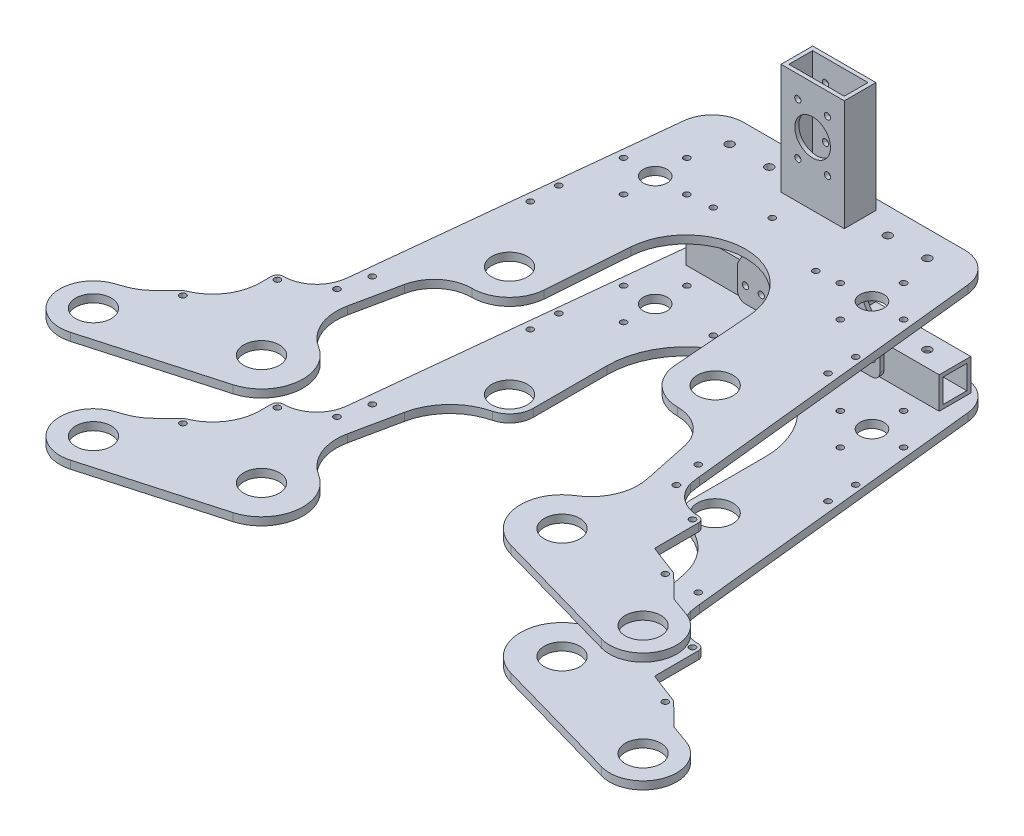
SolidWorks part; units mm, degrees
ref_plane "Alzado" through (0, 0, 0) normal (0, 0, 1) x (1, 0, 0)
ref_plane "Planta" through (0, 0, 0) normal (0, 1, 0) x (1, 0, 0)
ref_plane "Vista lateral" through (0, 0, 0) normal (1, 0, 0) x (0, 0, -1)
sketch "llantas" plane through (0, 0, 0) normal (0, 1, 0) x (1, 0, 0)
  line L0 (0, 221.5734) -> (0, 0) construction
  line L1 (-215.9, 0) -> (0, 0) construction
  circle A0 centre (-93.6625, 101.6) radius 50.8
  circle A1 centre (-215.9, 0) radius 38.1
  circle A2 centre (215.9, 0) radius 38.1
  circle A3 centre (93.6625, 101.6) radius 50.8
  dimension "D1" = 101.6
  dimension "D2" = 42.8625
  dimension "D3" = 177.8
  dimension "D4" = 76.2
  dimension "D5" = 101.6
sketch "cono" plane through (0, 0, 0) normal (1, 0, 0) x (0, 0, -1)
  line L0 (-76.2, 23.114) -> (-22.987, 324.358)
  line L1 (-22.987, 324.358) -> (22.987, 324.358)
  line L2 (0, 324.358) -> (0, 23.114) construction
  line L3 (76.2, 23.114) -> (-76.2, 23.114) construction
  line L4 (-76.2, 23.114) -> (-106.426, 23.114)
  line L5 (-106.426, 23.114) -> (-106.426, 0)
  line L6 (-106.426, 0) -> (106.426, 0)
  line L7 (0, 0) -> (0, 23.114)
  line L8 (-76.2, 23.114) -> (76.2, 23.114)
  line L9 (-80.283, 0) -> (80.283, 0)
  line L10 (221.5734, 0) -> (0, 0) construction
  line L11 (106.426, 23.114) -> (106.426, 0)
  line L12 (76.2, 23.114) -> (106.426, 23.114)
  line L13 (76.2, 23.114) -> (22.987, 324.358)
  line L14 (0, 220.8278) -> (41.275, 220.8278) construction
  dimension "D1" = 324.358
  dimension "D2" = 23.114
  dimension "D3" = 22.987
  dimension "D4" = 152.4
  dimension "D5" = 212.852
  dimension "D6" = 41.275
  dimension "D7" = 220.8278
sketch "Croquis4" plane through (0, 0, 0) normal (0, 1, 0) x (1, 0, 0)
  line L11 (0, 293.4478) -> (0, -300.8756) construction
  circle A36 centre (0, 179.087) radius 32.258
  dimension "D4" = 64.516
ref_plane "Plano1" through (0, 184.15, 0) normal (0, 1, 0) x (1, 0, 0)
sketch "Croquis11" plane through (0, 184.15, 0) normal (0, 1, 0) x (1, 0, 0)
  line L0 (0, -106.426) -> (0, 106.426) construction
  line L1 (-96.4967, 55.808) -> (-110.9593, -55.5389) construction
  line L2 (0, 0) -> (0, -47.7539) construction
  line L3 (-77.6831, 56.5481) -> (-54.5184, -53.3186) construction
  line L4 (-102.0644, -224.6803) -> (-63.9644, -63.6256) construction
  line L5 (-139.2356, -215.8869) -> (-101.1356, -54.8321) construction
  line L6 (0, 0) -> (-82.55, -59.2289) construction
  line L7 (0, 0) -> (0, -106.426) construction
  line L14 (-126.947, -202.253) -> (-226.9506, -237.178) construction
  line L15 (-114.353, -238.3143) -> (-214.3566, -273.2393) construction
  line L16 (0, 293.4478) -> (0, -300.8756) construction
  line L17 (-220.6536, -283.7836) -> (-120.65, -283.7836) construction
  circle A0 centre (0, 0) radius 47.7539 construction
  circle A1 centre (-82.55, -59.2289) radius 50.8
  circle A2 centre (-87.027, 54.578) radius 30
  arc A3 (-77.6831, 56.5481) -> (-96.4967, 55.808) centre (-87.027, 54.578) ccw construction
  arc A4 (-110.9593, -55.5389) -> (-54.5184, -53.3186) centre (-82.55, -59.2289) ccw construction
  arc A6 (-139.2356, -215.8869) -> (-102.0644, -224.6803) centre (-120.65, -220.2836) ccw construction
  arc A7 (-63.9644, -63.6256) -> (-101.1356, -54.8321) centre (-82.55, -59.2289) ccw construction
  circle A12 centre (-120.65, -220.2836) radius 50.8
  circle A13 centre (-220.6536, -255.2086) radius 28.575
  arc A14 (-226.9506, -237.178) -> (-214.3566, -273.2393) centre (-220.6536, -255.2086) ccw construction
  arc A15 (-114.353, -238.3143) -> (-139.2356, -215.8869) centre (-120.65, -220.2836) ccw construction
  dimension "D1" = 101.6
  dimension "D4" = 60
  dimension "D5" = 19.0986
  dimension "D6" = 57.2958
  dimension "D10" = 38.1972
  dimension "D17" = 101.6
  dimension "D13" = 57.15
  dimension "D14" = 38.1972
  dimension "D2" = 101.6
  dimension "D3" = 165.1
  dimension "D8" = 69.85
  dimension "D9" = 12.7
sketch "Croquis40" plane through (0, 184.15, 0) normal (0, 1, 0) x (1, 0, 0)
  line L0 (-117.475, -110.0289) -> (117.475, -110.0289) construction
  line L1 (-117.475, -110.0289) -> (-117.475, -344.9789) construction
  line L2 (117.475, -110.0289) -> (117.475, -344.9789) construction
  line L3 (-117.475, -344.9789) -> (117.475, -344.9789) construction
  line L4 (0, 0) -> (0, -110.0289)
  circle A1 centre (-82.55, -59.2289) radius 50.8 construction
  dimension "D1" = 234.95
ref_plane "Plano2" through (0, 95.25, 0) normal (0, 1, 0) x (1, 0, 0)
sketch "Croquis12" plane through (0, 95.25, 0) normal (0, 1, 0) x (1, 0, 0)
  line L0 (0, 0) -> (0, -63.4576) construction
  circle A0 centre (0, 0) radius 63.4576 construction
  circle A1 centre (-82.55, -59.2289) radius 50.8
  circle A2 centre (-82.55, -59.2289) radius 50.8 construction
sketch "Croquis42" plane through (0, 184.15, 0) normal (0, 1, 0) x (1, 0, 0)
  line L9 (-88.7823, 135.1003) -> (88.7949, 135.1003)
  line L10 (139.6816, -128.9028) -> (114.0528, 112.3831)
  line L11 (-47.6217, 3.5515) -> (-52.471, -61.4721)
  line L12 (-112.3836, -113.6275) -> (-120.3575, -151.7275)
  line L13 (-120.65, -220.2836) -> (-220.6536, -255.2086) construction
  line L14 (-111.5648, -252.3593) -> (-213.299, -281.1746)
  line L15 (0, 226.6032) -> (0, -226.6032) construction
  line L17 (229.5516, -229.7302) -> (214.7311, -224.4111)
  line L18 (-229.5516, -229.7302) -> (-215.5189, -224.8294)
  line L19 (-139.5373, -128.9308) -> (-114.0416, 112.3692)
  line L20 (-126.947, -202.253) -> (-226.9506, -237.178) construction
  line L22 (111.5648, -252.3593) -> (213.299, -281.1746)
  line L23 (112.3836, -113.6275) -> (120.3575, -151.7275)
  line L24 (47.6217, 3.5515) -> (52.471, -61.4721)
  circle A11 centre (-220.6536, -255.2086) radius 14.2875
  circle A17 centre (-120.65, -220.2836) radius 14.2875
  circle A18 centre (-82.55, -59.2289) radius 14.2875
  arc A20 (47.6217, 3.5515) -> (-47.6217, 3.5515) centre (0, 0) ccw
  circle A21 centre (87.027, 62.198) radius 25.4 construction
  circle A22 centre (0, 0) radius 47.7539 construction
  arc A23 (-82.55, -89.3914) -> (-52.471, -61.4721) centre (-82.55, -59.2289) ccw
  arc A24 (-82.55, -89.3914) -> (-112.3836, -113.6275) centre (-82.55, -119.8714) ccw
  arc A25 (-111.5648, -252.3593) -> (-103.1106, -191.933) centre (-120.65, -220.2836) ccw
  arc A26 (-120.3575, -151.7275) -> (-103.1106, -191.933) centre (-83.0655, -159.5323) ccw
  arc A28 (-229.5516, -229.7302) -> (-213.299, -281.1746) centre (-220.6536, -255.2086) ccw
  circle A29 centre (120.65, -220.2836) radius 33.3375 construction
  circle A30 centre (112.427, 62.198) radius 2.4892
  circle A33 centre (-120.65, -220.2836) radius 33.3375 construction
  circle A34 centre (-87.027, 62.198) radius 25.4 construction
  circle A35 centre (-87.027, 87.598) radius 2.4892
  circle A36 centre (-61.627, 62.198) radius 2.4892
  circle A37 centre (-87.027, 36.798) radius 2.4892
  circle A38 centre (-112.427, 62.198) radius 2.4892
  circle A39 centre (87.027, 36.798) radius 2.4892
  circle A40 centre (61.627, 62.198) radius 2.4892
  circle A41 centre (87.027, 87.598) radius 2.4892
  arc A43 (229.5516, -229.7302) -> (213.299, -281.1746) centre (220.6536, -255.2086) cw
  arc A44 (120.3575, -151.7275) -> (103.1106, -191.933) centre (83.0655, -159.5323) cw
  arc A45 (111.5648, -252.3593) -> (103.1106, -191.933) centre (120.65, -220.2836) cw
  arc A46 (82.55, -89.3914) -> (112.3836, -113.6275) centre (82.55, -119.8714) cw
  arc A47 (82.55, -89.3914) -> (52.471, -61.4721) centre (82.55, -59.2289) cw
  circle A48 centre (82.55, -59.2289) radius 14.2875
  circle A49 centre (120.65, -220.2836) radius 14.2875
  circle A50 centre (220.6536, -255.2086) radius 14.2875
  arc A52 (139.6816, -128.9028) -> (214.7311, -224.4111) centre (253.3422, -116.8301) ccw
  arc A53 (-215.5189, -224.8294) -> (-139.5373, -128.9308) centre (-253.2046, -116.9208) ccw
  circle A54 centre (-87.027, 62.198) radius 9.5631
  circle A55 centre (87.027, 62.198) radius 9.5631
  arc A56 (114.0528, 112.3831) -> (88.7949, 135.1003) centre (88.7949, 109.7003) ccw
  arc A57 (-114.0416, 112.3692) -> (-88.7823, 135.1003) centre (-88.7823, 109.7003) cw
  point P18 (0, 0)
  point P40 (111.6399, 135.1003)
  point P52 (-87.027, 62.198)
  point P66 (147.2539, -200.1933)
  point P82 (-111.6399, 135.1003)
  point P83 (0, 0)
  point P84 (0, 0)
  point P85 (87.027, 62.198)
  point P86 (0, 0)
  point P87 (0, 0)
  point P90 (-147.2539, -200.1933)
  point P92 (0, 0)
  dimension "D1" = 28.575
  dimension "D2" = 19.05
  dimension "D3" = 12.7
  dimension "D4" = 15.875
  dimension "D5" = 38.1
  dimension "D7" = 30.48
  dimension "D8" = 50.8
  dimension "D9" = 4.9784
  dimension "D11" = 114.3
  dimension "D12" = 19.1262
  dimension "D13" = 25.4
  dimension "D14" = 241.3
  dimension "D16" = 137.16
  dimension "D18" = 72.9022
  dimension "D19" = 87.027
  dimension "D6" = 38.1
  dimension "D17" = 1.766
  dimension "D10" = 4
extrude "4400-23-P-0501" add sketch "Croquis42" along normal blind 6.35
sketch "Croquis44" plane through (0, 95.25, 0) normal (0, 1, 0) x (1, 0, 0)
  line L1 (-114.0416, 112.3692) -> (-139.5373, -128.9308) construction
  line L3 (-114.0416, 112.3692) -> (-139.5373, -128.9308)
  line L4 (139.6816, -128.9028) -> (114.0528, 112.3831) construction
  line L5 (229.5516, -229.7302) -> (214.7311, -224.4111) construction
  line L6 (111.5648, -252.3593) -> (213.299, -281.1746) construction
  line L7 (112.3836, -113.6275) -> (120.3575, -151.7275) construction
  line L9 (88.7949, 135.1003) -> (-88.7823, 135.1003) construction
  line L10 (-120.3575, -151.7275) -> (-112.3836, -113.6275) construction
  line L11 (-213.299, -281.1746) -> (-111.5648, -252.3593) construction
  line L12 (-215.5189, -224.8294) -> (-229.5516, -229.7302) construction
  line L13 (139.6816, -128.9028) -> (114.0528, 112.3831)
  line L14 (229.5516, -229.7302) -> (214.7311, -224.4111)
  line L15 (111.5648, -252.3593) -> (213.299, -281.1746)
  line L16 (112.3836, -113.6275) -> (120.3575, -151.7275)
  line L19 (-120.3575, -151.7275) -> (-112.3836, -113.6275)
  line L20 (-213.299, -281.1746) -> (-111.5648, -252.3593)
  line L21 (-215.5189, -224.8294) -> (-229.5516, -229.7302)
  line L22 (-63.4576, -59.2289) -> (-63.4576, 0)
  line L23 (63.4576, -59.2289) -> (63.4576, 0)
  line L24 (0, 0) -> (0, -147.841) construction
  line L25 (88.7949, 135.1003) -> (-88.7823, 135.1003)
  arc A0 (-215.5189, -224.8294) -> (-139.5373, -128.9308) centre (-253.2046, -116.9208) ccw construction
  arc A2 (-215.5189, -224.8294) -> (-139.5373, -128.9308) centre (-253.2046, -116.9208) ccw
  arc A5 (139.6816, -128.9028) -> (214.7311, -224.4111) centre (253.3422, -116.8301) ccw construction
  arc A6 (213.299, -281.1746) -> (229.5516, -229.7302) centre (220.6536, -255.2086) ccw construction
  arc A7 (103.1106, -191.933) -> (111.5648, -252.3593) centre (120.65, -220.2836) ccw construction
  arc A8 (103.1106, -191.933) -> (120.3575, -151.7275) centre (83.0655, -159.5323) ccw construction
  arc A11 (114.0528, 112.3831) -> (88.7949, 135.1003) centre (88.7949, 109.7003) ccw construction
  arc A14 (-120.3575, -151.7275) -> (-103.1106, -191.933) centre (-83.0655, -159.5323) ccw construction
  arc A15 (-111.5648, -252.3593) -> (-103.1106, -191.933) centre (-120.65, -220.2836) ccw construction
  arc A16 (-229.5516, -229.7302) -> (-213.299, -281.1746) centre (-220.6536, -255.2086) ccw construction
  arc A18 (139.6816, -128.9028) -> (214.7311, -224.4111) centre (253.3422, -116.8301) ccw
  arc A19 (213.299, -281.1746) -> (229.5516, -229.7302) centre (220.6536, -255.2086) ccw
  arc A20 (103.1106, -191.933) -> (111.5648, -252.3593) centre (120.65, -220.2836) ccw
  arc A21 (103.1106, -191.933) -> (120.3575, -151.7275) centre (83.0655, -159.5323) ccw
  arc A27 (-120.3575, -151.7275) -> (-103.1106, -191.933) centre (-83.0655, -159.5323) ccw
  arc A28 (-111.5648, -252.3593) -> (-103.1106, -191.933) centre (-120.65, -220.2836) ccw
  arc A29 (-229.5516, -229.7302) -> (-213.299, -281.1746) centre (-220.6536, -255.2086) ccw
  circle A30 centre (87.027, 62.198) radius 9.5631 construction
  circle A31 centre (87.027, 36.798) radius 2.4892 construction
  circle A32 centre (112.427, 62.198) radius 2.4892 construction
  circle A33 centre (87.027, 87.598) radius 2.4892 construction
  circle A34 centre (61.627, 62.198) radius 2.4892 construction
  circle A35 centre (-87.027, 62.198) radius 9.5631 construction
  circle A37 centre (-87.027, 87.598) radius 2.4892 construction
  circle A38 centre (-112.427, 62.198) radius 2.4892 construction
  circle A39 centre (-87.027, 36.798) radius 2.4892 construction
  circle A40 centre (220.6536, -255.2086) radius 14.2875 construction
  circle A41 centre (120.65, -220.2836) radius 14.2875 construction
  circle A42 centre (82.55, -59.2289) radius 14.2875 construction
  circle A43 centre (-82.55, -59.2289) radius 14.2875 construction
  circle A44 centre (-120.65, -220.2836) radius 14.2875 construction
  circle A45 centre (-220.6536, -255.2086) radius 14.2875 construction
  circle A46 centre (87.027, 62.198) radius 9.5631
  circle A47 centre (87.027, 36.798) radius 2.4892
  circle A48 centre (112.427, 62.198) radius 2.4892
  circle A49 centre (87.027, 87.598) radius 2.4892
  circle A50 centre (61.627, 62.198) radius 2.4892
  circle A51 centre (-87.027, 62.198) radius 9.5631
  circle A53 centre (-87.027, 87.598) radius 2.4892
  circle A54 centre (-112.427, 62.198) radius 2.4892
  circle A55 centre (-87.027, 36.798) radius 2.4892
  circle A56 centre (220.6536, -255.2086) radius 14.2875
  circle A57 centre (120.65, -220.2836) radius 14.2875
  circle A58 centre (82.55, -59.2289) radius 14.2875
  circle A59 centre (-82.55, -59.2289) radius 14.2875
  circle A60 centre (-120.65, -220.2836) radius 14.2875
  circle A61 centre (-220.6536, -255.2086) radius 14.2875
  arc A62 (63.4576, 0) -> (-63.4576, 0) centre (0, 0) ccw
  arc A63 (-88.7823, 135.1003) -> (-114.0416, 112.3692) centre (-88.7823, 109.7003) ccw construction
  arc A64 (-63.4576, -59.2289) -> (-77.9, -77.7463) centre (-82.55, -59.2289) cw
  arc A65 (-112.3836, -113.6275) -> (-77.9, -77.7463) centre (-66.477, -123.2353) cw
  circle A66 centre (0, 0) radius 63.4576 construction
  arc A67 (112.3836, -113.6275) -> (77.9, -77.7463) centre (66.477, -123.2353) ccw
  arc A68 (63.4576, -59.2289) -> (77.9, -77.7463) centre (82.55, -59.2289) ccw
  arc A69 (114.0528, 112.3831) -> (88.7949, 135.1003) centre (88.7949, 109.7003) ccw
  arc A70 (-88.7823, 135.1003) -> (-114.0416, 112.3692) centre (-88.7823, 109.7003) ccw
extrude "4400-23-P-0502" add sketch "Croquis44" along normal blind 6.35
sketch "Croquis45" plane through (0, 95.25, 0) normal (0, -1, 0) x (1, 0, 0)
  line L7 (-126.947, 202.253) -> (-226.9506, 237.178) construction
  circle A0 centre (-189.6273, 213.7178) radius 4.7625 construction
  circle A1 centre (-189.6273, 213.7178) radius 2.4892
  circle A6 centre (-220.6536, 255.2086) radius 38.1
  circle A7 centre (-220.6536, 255.2086) radius 38.1 construction
  circle A9 centre (-120.65, 220.2836) radius 63.5
  circle A10 centre (-120.65, 220.2836) radius 63.5 construction
  dimension "D1" = 9.525
  dimension "D2" = 4.9784
  dimension "D5" = 5.08
  dimension "D3" = 9.525
  dimension "D4" = 12.7
sketch "Croquis46" plane through (0, 190.5, 0) normal (0, 1, 0) x (1, 0, 0)
  line L0 (-184.6841, -242.6467) -> (-180.5992, -241.2201) construction
  line L1 (-126.947, -202.253) -> (-226.9506, -237.178) construction
  line L2 (-220.6536, -255.2086) -> (-120.65, -220.2836) construction
  line L3 (-182.6417, -241.9334) -> (-193.6494, -210.4142) construction
  line L4 (-166.6601, -156.7836) -> (-120.65, -156.7836) construction
  line L5 (-215.1779, -224.7097) -> (-196.9699, -207.0002)
  line L6 (-171.5935, -196.9465) -> (-195.3397, -205.9618)
  line L7 (-171.5935, -196.9465) -> (-171.4226, -161.5232)
  line L8 (0, 0) -> (0, -195.4432) construction
  line L9 (166.6601, -156.7836) -> (120.65, -156.7836) construction
  line L10 (182.6417, -241.9334) -> (193.6494, -210.4142) construction
  line L11 (220.6536, -255.2086) -> (120.65, -220.2836) construction
  line L12 (184.6841, -242.6467) -> (180.5992, -241.2201) construction
  line L13 (171.524, -196.8756) -> (171.4226, -161.5232)
  line L14 (171.524, -196.8756) -> (195.3397, -205.9618)
  line L15 (215.1779, -224.7097) -> (196.9699, -207.0002)
  circle A0 centre (-220.6536, -255.2086) radius 38.1 construction
  circle A1 centre (-193.6494, -210.4142) radius 4.7625 construction
  circle A2 centre (-193.6494, -210.4142) radius 2.4892
  circle A3 centre (-166.6601, -161.5461) radius 4.7625 construction
  circle A4 centre (-166.6601, -161.5461) radius 2.4892
  arc A5 (-215.5189, -224.8294) -> (-139.5373, -128.9308) centre (-253.2046, -116.9208) ccw construction
  circle A6 centre (-120.65, -220.2836) radius 63.5 construction
  arc A7 (-196.9699, -207.0002) -> (-195.3397, -205.9618) centre (-193.6494, -210.4142) cw
  arc A8 (-171.4226, -161.5232) -> (-166.6601, -156.7836) centre (-166.6601, -161.5461) cw
  arc A9 (-166.6601, -156.7836) -> (-140.1904, -134.0169) centre (-166.6601, -130.0127) ccw
  arc A10 (-215.1779, -224.7097) -> (-140.1904, -134.0169) centre (-253.2046, -116.9208) ccw
  circle A11 centre (166.6601, -161.5461) radius 4.7625 construction
  circle A12 centre (193.6494, -210.4142) radius 4.7625 construction
  arc A13 (215.1779, -224.7097) -> (140.1904, -134.0169) centre (253.2046, -116.9208) cw
  arc A14 (166.6601, -156.7836) -> (140.1904, -134.0169) centre (166.6601, -130.0127) cw
  arc A15 (171.4226, -161.5232) -> (166.6601, -156.7836) centre (166.6601, -161.5461) ccw
  arc A16 (196.9699, -207.0002) -> (195.3397, -205.9618) centre (193.6494, -210.4142) ccw
  circle A17 centre (166.6601, -161.5461) radius 2.4892
  circle A18 centre (193.6494, -210.4142) radius 2.4892
  point P20 (-182.6417, -241.9334)
  point P59 (171.7892, -196.616)
  point P60 (0, 0)
  arc M29 (214.7311, -224.4111) -> (139.6816, -128.9028) centre (253.3422, -116.8301) cw
  arc M35 (-139.5373, -128.9308) -> (-215.5189, -224.8294) centre (-253.2046, -116.9208) cw
  dimension "D1" = 4.9784
  dimension "D2" = 9.525
  dimension "D4" = 6.35
  dimension "D3" = 9.525
  dimension "D5" = 25.4
extrude "Saliente-Extruir2" add sketch "Croquis46" against normal up to surface (6.35 mm away) contours A9 A8 L7 A4 M35 | A7 L5 A2 L6 M35 | L13 A15 A14 A17 M29 | A18 L15 A16 L14 M29 region at (-160.3128, 190.5, 168.9154) region at (-205.7136, 190.5, 216.2254) region at (171.6867, 190.5, 196.9931) region at (160.416, 190.5, 168.894) up to face at (-0.0173, 184.15, 113.2201)
fillet "Redondeo1" radius 38.1 2 edges at (-215.1779, 187.325, 224.7097) (-171.5935, 187.325, 196.9465)
extrude "Saliente-Extruir3" add sketch "Croquis46<3>" against normal up to surface (95.25 mm away) from surface contours A9 A8 L7 A4 M35 | A7 L5 A2 L6 M35 | L13 A15 A14 A17 M29 | A18 L15 A16 L14 M29 region at (-160.3128, 190.5, 168.9154) region at (-205.7136, 190.5, 216.2254) region at (171.6867, 190.5, 196.9931) region at (160.416, 190.5, 168.894) up to face at (-0.0173, 95.25, 111.4477) starting at face at (-120.65, 101.6, 234.5711)
sketch "Croquis46<3>" plane through (0, 190.5, 0) normal (0, 1, 0) x (1, 0, 0) same geometry as "Croquis46"
fillet "Redondeo2" radius 38.1 2 edges at (-215.1779, 98.425, 224.7097) (-171.5935, 98.425, 196.9465)
sketch "Croquis47" plane through (0, 190.5, 0) normal (0, 1, 0) x (1, 0, 0)
  line L0 (-139.2356, -215.8869) -> (-101.1356, -54.8321) construction
  line L1 (88.7949, 135.1003) -> (-88.7823, 135.1003) construction
  line L4 (0, 0) -> (0, -211.1114) construction
  line L9 (-96.4967, 55.808) -> (-110.9593, -55.5389) construction
  line L14 (-77.6831, 56.5481) -> (-54.5184, -53.3186) construction
  circle A0 centre (-136.2788, -144.0836) radius 4.7625 construction
  circle A1 centre (-136.2788, -144.0836) radius 2.4892
  circle A2 centre (-130.8514, -121.1414) radius 4.7625 construction
  circle A3 centre (-130.8514, -121.1414) radius 2.4892
  circle A5 centre (-120.65, -220.2836) radius 63.5 construction
  circle A7 centre (-82.55, -59.2289) radius 50.8 construction
  circle A8 centre (130.8514, -121.1414) radius 2.4892
  circle A9 centre (130.8514, -121.1414) radius 4.7625 construction
  circle A10 centre (136.2788, -144.0836) radius 2.4892
  circle A11 centre (136.2788, -144.0836) radius 4.7625 construction
  circle A12 centre (-119.5187, -5.5845) radius 2.4892
  circle A13 centre (-119.5187, -5.5845) radius 4.7625 construction
  circle A14 centre (-119.1503, 16.9711) radius 2.4892
  circle A15 centre (-119.1503, 16.9711) radius 4.7625 construction
  circle A17 centre (-87.027, 54.578) radius 30 construction
  circle A18 centre (119.1503, 16.9711) radius 4.7625 construction
  circle A19 centre (119.1503, 16.9711) radius 2.4892
  circle A20 centre (119.5187, -5.5845) radius 4.7625 construction
  circle A21 centre (119.5187, -5.5845) radius 2.4892
  circle A22 centre (-43.3745, 60.7655) radius 4.7625 construction
  circle A23 centre (-43.3745, 60.7655) radius 2.4892
  circle A24 centre (43.3745, 60.7655) radius 2.4892
  circle A25 centre (43.3745, 60.7655) radius 4.7625 construction
  circle A26 centre (-11.0144, 80.167) radius 4.7625 construction
  circle A27 centre (-11.0144, 80.167) radius 2.4892
  circle A28 centre (-41.8594, 63.6221) radius 2.4892
  circle A29 centre (-41.8594, 63.6221) radius 4.7625 construction
  circle A31 centre (0, 0) radius 63.4576 construction
  circle A32 centre (41.8594, 63.6221) radius 2.4892
  circle A33 centre (41.8594, 63.6221) radius 4.7625 construction
  dimension "D1" = 4.9784
  dimension "D2" = 9.525
  dimension "D3" = 8.89
  dimension "D4" = 8.89
  dimension "D5" = 12.7
  dimension "D6" = 6.35
  dimension "D7" = 9.525
  dimension "D8" = 4.9784
  dimension "D9" = 12.7
  dimension "D10" = 10.16
  dimension "D11" = 25.4
  dimension "D12" = 25.4
  dimension "D13" = 4.9784
  dimension "D14" = 9.525
  dimension "D15" = 8.89
  dimension "D16" = 74.3347
  dimension "D17" = 9.525
  dimension "D18" = 4.9784
  dimension "D19" = 12.7
  dimension "D20" = 65.3447
  dimension "D21" = 12.7
  dimension "D22" = 31.75
extrude "Cortar-Extruir1" cut sketch "Croquis47" against normal through all contours A27 | A19 | A21 | A8 | A10 | A1 | A14 | A12 | A23 A28 | A23 A28 | A3 | A24 region at (-136.2788, 190.5, 144.0836) region at (130.8514, 190.5, 121.1414) region at (136.2788, 190.5, 144.0836) region at (-119.5187, 190.5, 5.5845) region at (-119.1503, 190.5, -16.9711) region at (119.1503, 190.5, -16.9711) region at (119.5187, 190.5, 5.5845) region at (-42.6169, 190.5, -62.1938) region at (-41.6259, 190.5, -64.0622) region at (-11.0144, 190.5, -80.167)
sketch "Croquis48" plane through (0, 101.6, 0) normal (0, 1, 0) x (1, 0, 0)
  line L1 (-101.6, 127) -> (101.6, 127)
  line L2 (-101.6, 127) -> (-101.6, 101.6)
  line L3 (-101.6, 101.6) -> (101.6, 101.6)
  line L4 (101.6, 127) -> (101.6, 101.6)
  line L5 (-101.6, 127) -> (101.6, 101.6) construction
  line L6 (-101.6, 101.6) -> (101.6, 127) construction
  point P0 (0, 114.3)
  dimension "D1" = 25.4
  dimension "D2" = 203.2
  dimension "D3" = 114.3
extrude "Saliente-Extruir4" add sketch "Croquis48" along normal blind 25.4 from surface separate body starting at face at (119.1503, 101.6, -14.4819)
shell "Vaciado1" thickness 3.175 removed face at (-101.6, 114.3, -114.3) removed face at (101.6, 114.3, -114.3)
sketch "Croquis49" plane through (0, 127, 0) normal (0, 1, 0) x (1, 0, 0)
  line L0 (0, 127) -> (0, 101.6) construction
  line L1 (-101.6, 127) -> (101.6, 127) construction
  line L2 (101.6, 101.6) -> (-101.6, 101.6) construction
  line L3 (-101.6, 114.3) -> (0, 114.3) construction
  line L4 (-101.6, 101.6) -> (-101.6, 127) construction
  line L6 (-25.4, 101.6) -> (25.4, 101.6)
  line L7 (-25.4, 101.6) -> (-25.4, 127)
  line L8 (-25.4, 127) -> (25.4, 127)
  line L9 (25.4, 101.6) -> (25.4, 127)
  line L10 (-25.4, 101.6) -> (25.4, 127) construction
  line L11 (-25.4, 127) -> (25.4, 101.6) construction
  dimension "D1" = 50.8
extrude "Saliente-Extruir5" add sketch "Croquis49" along normal blind 152.4 separate body
shell "Vaciado2" thickness 3.175 removed face at (0, 279.4, -114.3) removed face at (0, 127, -114.3)
sketch "Croquis50" plane through (0, 0, -101.6) normal (0, 0, 1) x (1, 0, 0)
  line L0 (-47.6217, 184.15) -> (47.6217, 184.15) construction
  line L1 (0, 241.2619) -> (11.9062, 261.8841) construction
  line L2 (-25.4, 279.4) -> (25.4, 279.4) construction
  line L3 (0, 241.2619) -> (0, 279.4) construction
  circle A0 centre (0, 241.2619) radius 14.3129
  circle A1 centre (0, 241.2619) radius 23.8125 construction
  circle A2 centre (11.9062, 261.8841) radius 2.4892
  circle A3 centre (23.8125, 241.2619) radius 2.4892 construction
  circle A4 centre (11.9062, 220.6397) radius 2.4892
  circle A5 centre (-11.9063, 220.6397) radius 2.4892
  circle A6 centre (-23.8125, 241.2619) radius 2.4892 construction
  circle A7 centre (-11.9063, 261.8841) radius 2.4892
  dimension "D1" = 57.1119
  dimension "D2" = 28.6258
  dimension "D3" = 47.625
  dimension "D4" = 4.9784
  dimension "D6" = 23.8125
  dimension "D5" = 6
extrude "Cortar-Extruir2" cut sketch "Croquis50" against normal through all
sketch "Croquis53" plane through (0, 0, -101.6) normal (0, 0, 1) x (1, 0, 0)
  line L0 (-101.6, 114.3) -> (101.6, 114.3) construction
  line L1 (-101.6, 127) -> (-101.6, 101.6) construction
  line L2 (101.6, 127) -> (101.6, 101.6) construction
  line L3 (0, 114.3) -> (12.7, 114.3) construction
  line L4 (0, 114.3) -> (0, 279.4) construction
  line L5 (-25.4, 279.4) -> (25.4, 279.4) construction
  line L6 (-12.7, 114.3) -> (-12.7, 127) construction
  line L7 (50.8, 101.6) -> (-50.8, 101.6)
  line L9 (101.6, 101.6) -> (-101.6, 101.6) construction
  line L10 (-57.15, 107.95) -> (-57.15, 125.3481)
  line L11 (101.6, 127) -> (-101.6, 127) construction
  line L12 (-56.3451, 128.4425) -> (-27.2168, 180.6403)
  line L13 (-25.4, 279.4) -> (-25.4, 127) construction
  line L14 (-21.6717, 183.896) -> (21.6717, 183.896)
  line L15 (57.15, 107.95) -> (57.15, 125.3481)
  line L16 (56.3451, 128.4425) -> (27.2168, 180.6403)
  circle A0 centre (0, 114.3) radius 2.4892
  circle A1 centre (12.7, 114.3) radius 2.4892
  circle A2 centre (25.4, 114.3) radius 2.4892
  circle A3 centre (38.1, 114.3) radius 2.4892
  circle A4 centre (50.8, 114.3) radius 2.4892
  circle A5 centre (-50.8, 114.3) radius 2.4892
  circle A6 centre (-38.1, 114.3) radius 2.4892
  circle A7 centre (-25.4, 114.3) radius 2.4892
  circle A8 centre (-12.7, 114.3) radius 2.4892
  circle A10 centre (-12.7, 127) radius 2.4892 [skipped]
  circle A11 centre (12.7, 127) radius 2.4892 [skipped]
  circle A12 centre (-12.7, 139.7) radius 2.4892
  circle A13 centre (12.7, 139.7) radius 2.4892
  circle A14 centre (-12.7, 152.4) radius 2.4892
  circle A15 centre (12.7, 152.4) radius 2.4892
  circle A16 centre (-12.7, 165.1) radius 2.4892
  circle A17 centre (12.7, 165.1) radius 2.4892
  circle A18 centre (-12.7, 177.8) radius 2.4892
  circle A19 centre (12.7, 177.8) radius 2.4892
  arc A20 (57.15, 107.95) -> (50.8, 101.6) centre (50.8, 107.95) cw
  arc A21 (57.15, 125.3481) -> (56.3451, 128.4425) centre (50.8, 125.3481) ccw
  arc A22 (27.2168, 180.6403) -> (21.6717, 183.896) centre (21.6717, 177.546) ccw
  arc A23 (-27.2168, 180.6403) -> (-21.6717, 183.896) centre (-21.6717, 177.546) cw
  arc A24 (-57.15, 125.3481) -> (-56.3451, 128.4425) centre (-50.8, 125.3481) cw
  arc A25 (-50.8, 101.6) -> (-57.15, 107.95) centre (-50.8, 107.95) cw
  point P63 (0, 101.6)
  point P65 (0, 183.896)
  point P68 (57.15, 101.6)
  point P71 (57.15, 127)
  point P74 (25.4, 183.896)
  point P77 (-25.4, 183.896)
  point P80 (-57.15, 127)
  point P83 (-57.15, 101.6)
  dimension "D1" = 4.9784
  dimension "D4" = 6
  dimension "D8" = 6.35
  dimension "D3" = 12.7
  dimension "D5" = 12.7
  dimension "D6" = 6.096
  dimension "D7" = 6.35
  dimension "D2" = 5
extrude "Saliente-Extruir6" add sketch "Croquis53" along normal blind 3.175 separate body
sketch "Croquis55" plane through (0, 0, -98.425) normal (0, 0, 1) x (1, 0, 0)
  circle A0 centre (-12.7, 114.3) radius 2.4892 construction
  circle A1 centre (-12.7, 139.7) radius 2.4892 construction
  circle A2 centre (-25.4, 114.3) radius 2.4892 construction
  circle A3 centre (-38.1, 114.3) radius 2.4892 construction
  circle A4 centre (-50.8, 114.3) radius 2.4892 construction
  circle A5 centre (-12.7, 114.3) radius 2.4892
  circle A6 centre (-12.7, 139.7) radius 2.4892
  circle A7 centre (-25.4, 114.3) radius 2.4892
  circle A8 centre (-38.1, 114.3) radius 2.4892
  circle A9 centre (-50.8, 114.3) radius 2.4892
  circle A10 centre (-12.7, 165.1) radius 2.4892 construction
  circle A11 centre (-12.7, 152.4) radius 2.4892 construction
  circle A12 centre (-12.7, 165.1) radius 2.4892
  circle A13 centre (-12.7, 152.4) radius 2.4892
  circle A14 centre (-12.7, 177.8) radius 2.4892 construction
  circle A15 centre (-12.7, 177.8) radius 2.4892
  circle A16 centre (12.7, 165.1) radius 2.4892 construction
  circle A17 centre (12.7, 177.8) radius 2.4892 construction
  circle A18 centre (12.7, 165.1) radius 2.4892
  circle A19 centre (12.7, 177.8) radius 2.4892
  circle A20 centre (0, 114.3) radius 2.4892 construction
  circle A21 centre (12.7, 114.3) radius 2.4892 construction
  circle A22 centre (12.7, 139.7) radius 2.4892 construction
  circle A23 centre (12.7, 152.4) radius 2.4892 construction
  circle A24 centre (0, 114.3) radius 2.4892
  circle A25 centre (12.7, 114.3) radius 2.4892
  circle A26 centre (12.7, 139.7) radius 2.4892
  circle A27 centre (12.7, 152.4) radius 2.4892
  circle A28 centre (50.8, 114.3) radius 2.4892 construction
  circle A29 centre (38.1, 114.3) radius 2.4892 construction
  circle A30 centre (25.4, 114.3) radius 2.4892 construction
  circle A31 centre (50.8, 114.3) radius 2.4892
  circle A32 centre (38.1, 114.3) radius 2.4892
  circle A33 centre (25.4, 114.3) radius 2.4892
extrude "Cortar-Extruir3" cut sketch "Croquis55" against normal up to surface (28.575 mm away) up to face at (-9.417, 261.8841, -127)
sketch "Croquis56" plane through (0, 101.6, 0) normal (0, -1, 0) x (1, 0, 0)
  line L0 (0, -101.6) -> (0, -127) construction
  line L1 (101.6, -101.6) -> (-101.6, -101.6) construction
  line L2 (-101.6, -127) -> (101.6, -127) construction
  line L3 (0, -114.3) -> (-101.6, -114.3) construction
  line L4 (-101.6, -101.6) -> (-101.6, -127) construction
  line L5 (-25.4, -114.3) -> (-25.4, -127) construction
  circle A0 centre (-47.625, -114.3) radius 3.2639
  circle A1 centre (-79.375, -114.3) radius 3.2639
  circle A2 centre (79.375, -114.3) radius 3.2639
  circle A3 centre (47.625, -114.3) radius 3.2639
  dimension "D1" = 25.4
  dimension "D2" = 6.5278
  dimension "D3" = 31.75
  dimension "D4" = 22.225
extrude "Cortar-Extruir4" cut sketch "Croquis56" against normal through all and the other way through all
sketch "Croquis57" plane through (0, 190.5, 0) normal (0, 1, 0) x (1, 0, 0)
  line L5 (0, 123.825) -> (0, 104.775) construction
  line L6 (22.225, 123.825) -> (-22.225, 123.825) construction
  line L7 (-22.225, 104.775) -> (22.225, 104.775) construction
  line L9 (-25.4381, 101.5619) -> (25.4381, 101.5619)
  line L10 (-25.4381, 101.5619) -> (-25.4381, 127.0381)
  line L11 (-25.4381, 127.0381) -> (25.4381, 127.0381)
  line L12 (25.4381, 101.5619) -> (25.4381, 127.0381)
  line L13 (-25.4381, 101.5619) -> (25.4381, 127.0381) construction
  line L14 (-25.4381, 127.0381) -> (25.4381, 101.5619) construction
  point P6 (0, 114.3)
  dimension "D1" = 25.4762
  dimension "D2" = 50.8762
extrude "Cortar-Extruir5" cut sketch "Croquis57" against normal up to next (6.35 mm away)
equation "\"D5@Croquis11\"=12*5MM/PI"
equation "\"D6@Croquis11\"=36*5mm/pi"
equation "\"D7@Croquis11\"=(70*5mm)+1mm"
equation "\"D10@Croquis11\"=24*5mm/pi"
equation "\"D11@Croquis11\"=(90*5mm)+1mm"
equation "\"D14@Croquis11\"=24*5mm/pi"
equation "\"D15@Croquis11\"=(70*5mm)+1mm"
